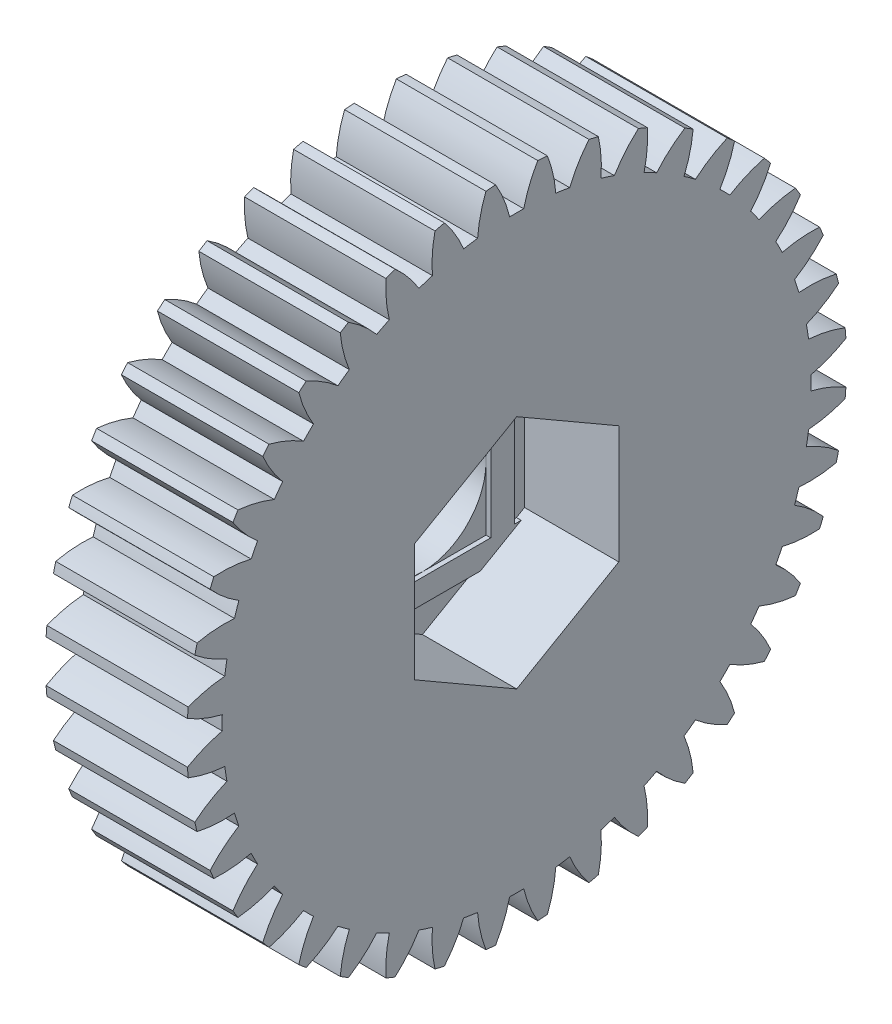
SolidWorks part; units mm, degrees
ref_plane "Plane1" through (0, 0, 0) normal (0, 0, 1) x (1, 0, 0)
ref_plane "Plane2" through (0, 0, 0) normal (0, 1, 0) x (1, 0, 0)
ref_plane "Plane3" through (0, 0, 0) normal (1, 0, 0) x (0, 0, -1)
sketch "HoldingSke" plane through (0, 0, 0) normal (0, 1, 0) x (1, 0, 0)
  line L0 (0, 0) -> (0.766, -0.6428)
  line L1 (-15, 0) -> (100, 0) construction
  line L2 (0, 0) -> (-2.1039, 2.3779)
  line L3 (0, 0) -> (-11.863, 4.5341)
  line L4 (0, 0) -> (6.6156, 5.5511)
  line L5 (0, 0) -> (-46.8476, -17.4728)
  line L6 (0, 0) -> (-7.4607, -5.0337)
  line L7 (-2.1039, 2.3779) -> (8.6586, 51.2059)
  line L8 (-76.2, 54.61) -> (-75.5, 54.61)
  line L9 (-71.009, 38.7566) -> (-53.1078, 45.2721)
  line L10 (-76.2, 71.12) -> (104.1128, 71.12)
  line L11 (0, 0) -> (-9, 0)
  line L12 (-76.2, 101.6) -> (-76.162, 101.6)
  line L13 (24.9733, 27.94) -> (52.9518, 28.4284)
  line L14 (24.9733, 27.94) -> (24.9743, 27.94)
  line L15 (24.9733, 27.94) -> (100.4006, 29.5858)
  line L16 (-63.627, -1) -> (-12.827, -1)
  circle A0 centre (0, 0) radius 2
  circle A1 centre (0, 0) radius 18.749
  circle A2 centre (0, 0) radius 37.5
  circle A3 centre (0, 0) radius 2
  dimension "MHD" = 37.498
  dimension "Hub_dia" = 75
  dimension "Bore" = 4
  dimension "MBD" = 4
  dimension "Num_teeth" = 40
  dimension "Pitch" = 1
  dimension "Overall_len" = 50
  dimension "Show_teeth" = 40
  dimension "Thickness" = 9
  dimension "OAL" = 50.0001
  dimension "T_dim" = 0.7
  dimension "Ap" = 20
  dimension "H" = 19.05
  dimension "Pitch_radius" = 180.3128
  dimension "Width" = 9
  dimension "Backlash" = 0.038
  dimension "Addendum_fac" = 1
  dimension "Dedendum_fac" = 1.25
  dimension "Clearance_fac" = 0.25
  dimension "Dedendum_add" = 0.001
  dimension "Module" = 1
sketch "BasProSke" plane through (0, 0, 0) normal (0, 1, 0) x (1, 0, 0)
  line L0 (-10, 0) -> (60, 0) construction
  line L1 (0, 0) -> (0, 21)
  line L2 (0, 0) -> (9, 0)
  line L3 (9, 0) -> (9, 21)
  line L4 (9, 21) -> (0, 21)
  dimension "Thickness" = 9
  dimension "Diameter" = 42
revolve "Base-Revolve" add sketch "BasProSke" angle 360 about L0
sketch "TooCutSke" plane through (0, 0, 0) normal (1, 0, 0) x (0, 0, -1)
  line L1 (0, 0) -> (0, 107) construction
  line L2 (0, 0) -> (-0.8517, 19.9819) construction
  line L3 (0, 0) -> (-3.1363, 39.8509) construction
  line L4 (-0.8517, 19.9819) -> (-1.5682, 19.9255) construction
  arc A0 (0.4487, 18.7436) -> (-0.4487, 18.7436) centre (0, 0) ccw
  arc A1 (1.3547, 20.9817) -> (-1.3547, 20.9817) centre (0, 0) ccw
  circle A2 centre (0, 0) radius 20 construction
  circle A3 centre (0, 0) radius 18.7939 construction
  arc A4 (-0.4487, 18.7436) -> (-1.3547, 20.9817) centre (-8.2322, 16.895) ccw
  arc A5 (1.3547, 20.9817) -> (0.4487, 18.7436) centre (8.2322, 16.895) ccw
  dimension "Root_dia" = 37.498
  dimension "Overcut_dia" = 42.0508
  dimension "Pitch_dia" = 40
  dimension "Base_dia" = 37.5877
  dimension "Flank_rad" = 8
  dimension "Half_ang" = 4.5
  dimension "Half_CT" = 0.7187
extrude "ToothCut" cut sketch "TooCutSke" along normal through all
fillet "Breaks" [suppressed] radius 0.02 tangent propagation no
fillet "RootFillets" [suppressed] radius 0.251
pattern_circular "TeethCuts" count 40 every 9 about axis through (-10, 0, 0) along (1, 0, 0) of "ToothCut", "RootFillets", "Breaks"
sketch "HubNeaOneSke" plane through (0, 0, 0) normal (-1, 0, 0) x (0, 0, 1)
  circle A0 centre (0, 0) radius 18.749
  dimension "Diameter" = 37.498
extrude "HubNearOne" [suppressed] add sketch "HubNeaOneSke" along normal blind 41.0001
sketch "HubNeaBotSke" plane through (0, 0, 0) normal (-1, 0, 0) x (0, 0, 1)
  circle A0 centre (0, 0) radius 18.749
  dimension "Diameter" = 37.498
extrude "HubNearBoth" [suppressed] add sketch "HubNeaBotSke" along normal blind 20.5
ref_plane "FarPln" through (9, 0, 0) normal (1, 0, 0) x (0, 0, -1)
sketch "HubFarSke" plane through (9, 0, 0) normal (1, 0, 0) x (0, 0, -1)
  circle A0 centre (0, 0) radius 18.749
  dimension "Diameter" = 37.498
extrude "HubFar" [suppressed] add sketch "HubFarSke" along normal blind 20.5
sketch "BorSke" plane through (0, 0, 0) normal (1, 0, 0) x (0, 0, -1)
  circle A0 centre (0, 0) radius 2
extrude "Bore" cut sketch "BorSke" along normal mid plane 100.0001
sketch "KeySke" plane through (0, 0, 0) normal (1, 0, 0) x (0, 0, -1)
  line L0 (-0.8, 0) -> (-0.8, 2.7)
  line L1 (-0.8, 2.7) -> (0.8, 2.7)
  line L2 (0.8, 2.7) -> (0.8, 0)
  line L3 (0, 0) -> (0, 34) construction
  line L4 (-0.8, 0) -> (0.8, 0)
  dimension "Offset" = 2.7
  dimension "Width" = 1.6
extrude "Keyway" [suppressed] cut sketch "KeySke" along normal mid plane 100.0001
pattern_circular "Keyway2" [suppressed] count 2 every 90 about axis through (-10, 0, 0) along (1, 0, 0)
sketch "Sketch1" plane through (9, 0, 0) normal (1, 0, 0) x (0, 0, -1)
  line L1 (0, 7.5056) -> (-6.5, 3.7528)
  line L2 (-6.5, 3.7528) -> (-6.5, -3.7528)
  line L3 (-6.5, -3.7528) -> (0, -7.5056)
  line L4 (0, -7.5056) -> (6.5, -3.7528)
  line L5 (6.5, -3.7528) -> (6.5, 3.7528)
  line L6 (6.5, 3.7528) -> (0, 7.5056)
  circle A0 centre (0, 0) radius 7.5056
  circle A2 centre (0, 0) radius 6.5 construction
  circle A3 centre (0, 0) radius 4.05
  dimension "D1" = 8.1
  dimension "D2" = 13
extrude "Cut-Extrude1" cut sketch "Sketch1" against normal blind 6 contours L1 L2 L3 L4 L5 L6
extrude "Cut-Extrude2" cut sketch "Sketch1<7>" against normal through all contours A3 region at (9, 0, 0)
sketch "Sketch1<7>" plane through (9, 0, 0) normal (1, 0, 0) x (0, 0, -1) same geometry as "Sketch1"
sketch "Sketch2" plane through (0, 0, 0) normal (-1, 0, 0) x (0, 0, 1)
  circle A0 centre (0, 0) radius 6.5
  circle A1 centre (0, 0) radius 4
  dimension "D1" = 13
  dimension "D2" = 8
extrude "Boss-Extrude1" add sketch "Sketch2" along normal blind 1.8
sketch "Sketch3" plane through (3, 0, 0) normal (1, 0, 0) x (0, 0, -1)
  line L1 (4.05, 4.05) -> (-4.05, 4.05)
  line L2 (4.05, 4.05) -> (4.05, -4.05)
  line L3 (4.05, -4.05) -> (-4.05, -4.05)
  line L4 (-4.05, 4.05) -> (-4.05, -4.05)
  line L6 (5.55, 5.55) -> (5.55, -5.55)
  line L7 (5.55, -5.55) -> (-5.55, -5.55)
  line L8 (-5.55, 5.55) -> (-5.55, -5.55)
  line L9 (5.55, 5.55) -> (-5.55, 5.55)
  line L10 (5.55, 4.05) -> (5.9852, 4.05)
  line L11 (6.5, 3.7528) -> (0, 7.5056) construction
  line L12 (5.55, -4.05) -> (5.9852, -4.05)
  line L13 (0, -7.5056) -> (6.5, -3.7528) construction
  line L14 (-5.55, -4.05) -> (-5.9852, -4.05)
  line L15 (-6.5, -3.7528) -> (0, -7.5056) construction
  line L16 (-5.55, 4.05) -> (-5.9852, 4.05)
  line L17 (0, 7.5056) -> (-6.5, 3.7528) construction
  circle A0 centre (0, 0) radius 4.05 construction
  line M10 (6.5, 3.7528) -> (0, 7.5056)
  line M11 (0, 7.5056) -> (-6.5, 3.7528)
  line M13 (-6.5, -3.7528) -> (0, -7.5056)
  line M14 (0, -7.5056) -> (6.5, -3.7528)
  dimension "D1" = 1.5
extrude "Boss-Extrude2" add sketch "Sketch3" along normal blind 0.3 contours L9 L8 L7 L6 L4 L1 L2 L3 M10 M11 M13 M14 | L12 L6 M14 | L6 L10 M10 | L16 L8 M11 | L8 L14 M13 region at (3, 0, -5.393) region at (3, 4.1338, -5.6951) region at (3, -4.1338, -5.6951) region at (3, 4.1338, 5.6951) region at (3, -4.1338, 5.6951)
equation "' \"Module@HoldingSke\" = 6.35"
equation "' \"Num_teeth@HoldingSke\" = 12"
equation "' \"Ap@HoldingSke\" =  20"
equation "' \"Ap@HoldingSke\" = 20"
equation "' \"Width@HoldingSke\" = 0.5 * 25.4"
equation "' \"Hub_dia@HoldingSke\"= 1 * 25.4"
equation "' \"Hub_dia@HoldingSke\" = 1 * 25.4"
equation "' \"Overall_len@HoldingSke\" = 1.0 * 25.4"
equation "' \"Bore@HoldingSke\" = 0.75 * 25.4"
equation "' \"T_dim@HoldingSke\" = 0.1 * 25.4"
equation "' \"Width@KeySke\" = 0.25 * 25.4"
equation "' \"Show_teeth@HoldingSke\" = 13"
equation "' \"Backlash@HoldingSke\" = 0.009 * 25.4"
equation "' \"Addendum_fac@HoldingSke\" = 1.0"
equation "' \"Dedendum_fac@HoldingSke\" = 1.25"
equation "' \"Dedendum_add@HoldingSke\" = 0.00005 * 25.4"
equation "' \"Clearance_fac@HoldingSke\" = 0.25"
equation "\"Pitch@HoldingSke\" = 1 / \"Module@HoldingSke\""
equation "\"Overcut_dia@TooCutSke\" = (\"Num_teeth@HoldingSke\" + 2 * \"Addendum_fac@HoldingSke\") / \"Pitch@HoldingSke\" + 0.002 * 25.4"
equation "\"Pitch_dia@TooCutSke\" = \"Num_teeth@HoldingSke\" / \"Pitch@HoldingSke\""
equation "\"Base_dia@TooCutSke\" = \"Num_teeth@HoldingSke\" / \"Pitch@HoldingSke\" * cos((\"Ap@HoldingSke\"  * 3.14159265 / 180))"
equation "\"Root_dia@TooCutSke\" = (\"Num_teeth@HoldingSke\" + 2) / \"Pitch@HoldingSke\" - 2 * (\"Addendum_fac@HoldingSke\" + \"Dedendum_fac@HoldingSke\") / \"Pitch@HoldingSke\" - \"Dedendum_add@HoldingSke\" * 2"
equation "\"Half_ang@TooCutSke\" = 180 / \"Num_teeth@HoldingSke\""
equation "\"Half_CT@TooCutSke\" = \"Num_teeth@HoldingSke\" / \"Pitch@HoldingSke\" * sin((3.14159265 / 2 / \"Num_teeth@HoldingSke\")) / 2 - 7 * \"Backlash@HoldingSke\" / 4"
equation "\"Flank_rad@TooCutSke\" = \"Num_teeth@HoldingSke\" / \"Pitch@HoldingSke\" / 5"
equation "\"Radius@RootFillets\" = \"Clearance_fac@HoldingSke\" / \"Pitch@HoldingSke\" + \"Dedendum_add@HoldingSke\""
equation "\"Break_rad@Breaks\" = 0.02 / \"Pitch@HoldingSke\""
equation "\"Thickness@HoldingSke\" = \"Width@HoldingSke\""
equation "\"OAL@HoldingSke\" = \"Thickness@HoldingSke\""
equation "\"MHD@HoldingSke\" = (\"Num_teeth@HoldingSke\" + 2) / \"Pitch@HoldingSke\" - 2 * (\"Addendum_fac@HoldingSke\" + \"Dedendum_fac@HoldingSke\")  / \"Pitch@HoldingSke\" - \"Dedendum_add@HoldingSke\" * 2"
equation "\"MBD@HoldingSke\" = (\"Num_teeth@HoldingSke\" + 2) / \"Pitch@HoldingSke\" - 2 * (\"Addendum_fac@HoldingSke\" + \"Dedendum_fac@HoldingSke\")  / \"Pitch@HoldingSke\" - \"Dedendum_add@HoldingSke\" * 2 - 0.002 * 25.4"
equation "\"MHD@HoldingSke\" = ((sgn( \"MHD@HoldingSke\" - \"Hub_dia@HoldingSke\" )-1)*( \"MHD@HoldingSke\" - \"Hub_dia@HoldingSke\" ))/-2+ \"Hub_dia@HoldingSke\""
equation "\"MBD@HoldingSke\" = ((sgn( \"MBD@HoldingSke\" - \"Bore@HoldingSke\" )-1)*( \"MBD@HoldingSke\" - \"Bore@HoldingSke\" ))/-2+ \"Bore@HoldingSke\""
equation "\"OAL@HoldingSke\" = ((sgn( \"OAL@HoldingSke\" - \"Overall_len@HoldingSke\" )+1)*( \"OAL@HoldingSke\" - \"Overall_len@HoldingSke\" ))/2 + \"Overall_len@HoldingSke\" + 0.000002 * 25.4"
equation "\"Num_teeth@TeethCuts\" = int( \"Show_teeth@HoldingSke\" ) + 1"
equation "\"Num_teeth@TeethCuts\" = ((sgn( \"Num_teeth@TeethCuts\" - \"Num_teeth@HoldingSke\" )-1)*( \"Num_teeth@TeethCuts\" - \"Num_teeth@HoldingSke\" ))/-2+ \"Num_teeth@HoldingSke\""
equation "\"Num_teeth@TeethCuts\" = ((sgn( \"Num_teeth@TeethCuts\" - 2.0)+1)*( \"Num_teeth@TeethCuts\" - 2.0))/2 +2.0"
equation "\"Angle@TeethCuts\" = 360.0 / \"Num_teeth@HoldingSke\""
equation "\"Diameter@BasProSke\" = (\"Num_teeth@HoldingSke\" + 2 * \"Addendum_fac@HoldingSke\") / \"Pitch@HoldingSke\""
equation "\"Thickness@BasProSke\"  = \"Thickness@HoldingSke\""
equation "' \"Fillet_rad@BasProSke\" =  \"Thickness@HoldingSke\" * 0.05"
equation "' \"Fillet_rad@BasProSke\" = \"Thickness@HoldingSke\" * 0.05"
equation "\"MHD@HoldingSke\" = ((sgn( \"MHD@HoldingSke\" - \"Root_dia@TooCutSke\" )-1)*( \"MHD@HoldingSke\" - \"Root_dia@TooCutSke\" ))/-2+ \"Root_dia@TooCutSke\""
equation "\"Diameter@HubNeaOneSke\" = \"MHD@HoldingSke\""
equation "\"Length@HubNearOne\" = \"OAL@HoldingSke\" - \"Thickness@BasProSke\""
equation "\"Diameter@HubNeaBotSke\" = \"MHD@HoldingSke\""
equation "\"Length@HubNearBoth\" = ( \"OAL@HoldingSke\" - \"Thickness@BasProSke\" ) / 2.0"
equation "\"Thickness@FarPln\" = \"Thickness@BasProSke\""
equation "\"Diameter@HubFarSke\" = \"MHD@HoldingSke\""
equation "\"Length@HubFar\" = ( \"OAL@HoldingSke\" - \"Thickness@BasProSke\" ) / 2.0"
equation "\"Diameter@BorSke\" = \"MBD@HoldingSke\""
equation "\"D1@Bore\" = \"OAL@HoldingSke\" * 2.0"
equation "\"D1@Keyway\" = \"OAL@HoldingSke\" * 2.0"
equation "\"Offset@KeySke\" = \"T_dim@HoldingSke\" + \"MBD@HoldingSke\" / 2.0"
